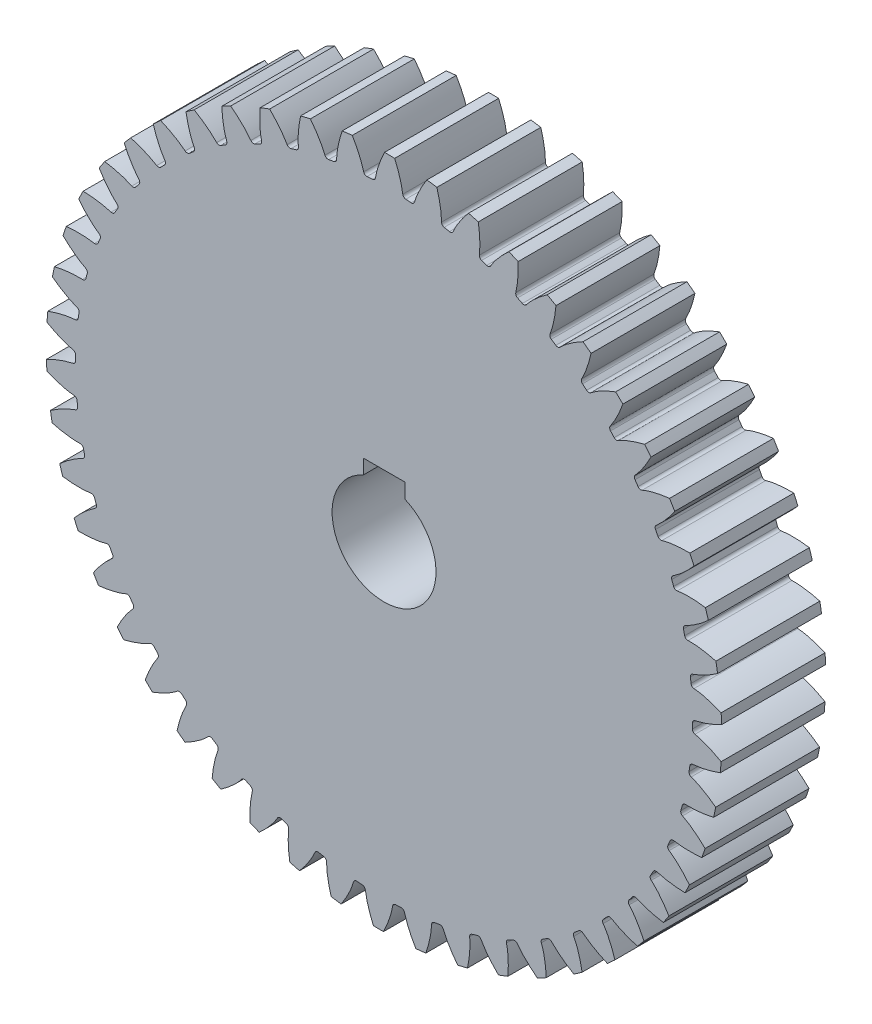
SolidWorks part; units mm, degrees
material "普通碳钢"
ref_plane "前视基准面" through (0, 0, 0) normal (0, 0, 1) x (1, 0, 0)
ref_plane "上视基准面" through (0, 0, 0) normal (0, 1, 0) x (1, 0, 0)
ref_plane "右视基准面" through (0, 0, 0) normal (1, 0, 0) x (0, 0, -1)
sketch "草图1" plane through (0, 0, 0) normal (0, 0, 1) x (1, 0, 0)
  circle A0 centre (0, 0) radius 65
  circle A1 centre (0, 0) radius 58.7308 construction
  spline S0 degree 4 poles (58.7308, 0) (58.7742, 0.0009) (58.8959, 0.0063) (59.1254, 0.0278) (59.4985, 0.0787) (59.9709, 0.1669) (60.577, 0.3073) (61.2842, 0.5066) (62.0529, 0.7609) (62.8786, 1.0748) (63.6921, 1.4211) (64.4927, 1.7963) (65.2805, 2.1977) (66.2209, 2.714) (67.331, 3.3787) (68.596, 4.2132) (69.9973, 5.2379) (71.3756, 6.3466) (72.7044, 7.5127) (73.8255, 8.5807) (74.7551, 9.5242) (75.5121, 10.3328) (76.1021, 10.9847) (76.8333, 11.8258) (77.5305, 12.661) (78.2319, 13.5487) (79.0118, 14.5714) (79.6995, 15.5266) (80.2633, 16.3317) (80.9464, 17.3657) (81.2887, 17.8975) (81.7628, 18.6537) (82.105, 19.2202) (82.4129, 19.7373) (82.5809, 20.0293) (82.6794, 20.1994) knots 0 0 0 0 0 0.005377 0.015084 0.028532 0.04661 0.064855 0.092111 0.119476 0.146842 0.174209 0.201575 0.228941 0.256307 0.307035 0.361767 0.4165 0.471232 0.525964 0.580697 0.608063 0.635429 0.662795 0.690161 0.744894 0.77226 0.799626 0.854358 0.881725 0.909091 0.931818 0.954545 0.977273 1 1 1 1 1 construction
  spline S1 degree 4 poles (58.7308, 0) (58.7742, 0.0009) (58.8959, 0.0063) (59.1254, 0.0278) (59.4985, 0.0787) (59.9709, 0.1669) (60.577, 0.3073) (61.2842, 0.5066) (62.0529, 0.7609) (62.8786, 1.0748) (63.6921, 1.4211) (64.4927, 1.7963) (65.2805, 2.1977) (66.2209, 2.714) (67.331, 3.3787) (68.596, 4.2132) (69.9973, 5.2379) (71.3756, 6.3466) (72.7044, 7.5127) (73.8255, 8.5807) (74.7551, 9.5242) (75.5121, 10.3328) (76.1021, 10.9847) (76.8333, 11.8258) (77.5305, 12.661) (78.2319, 13.5487) (79.0118, 14.5714) (79.6995, 15.5266) (80.2633, 16.3317) (80.829, 17.1879) (81.0441, 17.5188) (81.1526, 17.6879) knots 0 0 0 0 0 0.005377 0.015084 0.028532 0.04661 0.064855 0.092111 0.119476 0.146842 0.174209 0.201575 0.228941 0.256307 0.307035 0.361767 0.4165 0.471232 0.525964 0.580697 0.608063 0.635429 0.662795 0.690161 0.744894 0.77226 0.799626 0.854358 0.881725 0.909091 0.909091 0.909091 0.909091 0.909091 construction
  dimension "D1" = 130
  dimension "D2" = 117.4616
  dimension "D3" = 81.1526
extrude "凸台-拉伸1" add sketch "草图1" along normal blind 20
sketch "草图2" plane through (0, 0, 0) normal (0, 0, -1) x (-1, 0, 0)
  line L0 (0, 0) -> (-50000, 0) construction
  line L1 (24.9972, -0.3726) -> (-49969.4494, 744.8171) construction
  line L2 (0, 0) -> (-49970.4107, -825.1655) construction
  circle A0 centre (0, 0) radius 62.5 construction
  arc A1 (-59.375, 0.064) -> (-59.3405, -2.0244) centre (0, 0) ccw
  circle A2 centre (0, 0) radius 65 construction
  arc A3 (-64.9679, 2.0412) -> (-64.8651, -4.1851) centre (0, 0) ccw
  spline S0 degree 4 poles (-46.437, 1999.7444) (-50.1799, 43.412) (-53.349, 0.8372) (-56.4488, -0.3376) (-59.4985, 0.0787) (-59.9709, 0.1669) (-60.577, 0.3073) (-61.2842, 0.5066) (-62.0529, 0.7609) (-62.8786, 1.0748) (-63.6921, 1.4211) (-64.4927, 1.7963) (-65.2805, 2.1977) (-66.2209, 2.714) (-67.331, 3.3787) (-68.596, 4.2132) (-69.9973, 5.2379) (-71.3756, 6.3466) (-72.7044, 7.5127) (-73.8255, 8.5807) (-74.7551, 9.5242) (-75.5121, 10.3328) (-76.1021, 10.9847) (-76.8333, 11.8258) (-77.5305, 12.661) (-78.2319, 13.5487) (-79.0118, 14.5714) (-79.6995, 15.5266) (-81.7505, 18.4555) (-85.807, 25.1428) (-48.7954, -31.7441) (-1160.744, 1701.0672) knots -0.334457 -0.334457 -0.334457 -0.334457 -0.334457 0.005377 0.015084 0.028532 0.04661 0.064855 0.092111 0.119476 0.146842 0.174209 0.201575 0.228941 0.256307 0.307035 0.361767 0.4165 0.471232 0.525964 0.580697 0.608063 0.635429 0.662795 0.690161 0.744894 0.77226 0.799626 0.854358 0.881725 1.270064 1.270064 1.270064 1.270064 1.270064 only from (-58.7308, 0) to (-81.1526, 17.6879) construction
  spline S1 degree 4 poles (-59.375, 0.064) (-59.4427, 0.0741) (-59.6545, 0.108) (-60.01, 0.1759) (-60.577, 0.3073) (-61.2842, 0.5066) (-62.0529, 0.7609) (-62.8786, 1.0748) (-63.6921, 1.4211) (-64.3135, 1.7123) (-64.73, 1.9194) (-64.9474, 2.0306) (-64.9679, 2.0412) knots 0.020053 0.020053 0.020053 0.020053 0.020053 0.028532 0.04661 0.064855 0.092111 0.119476 0.146842 0.174209 0.201575 0.20444 0.20444 0.20444 0.20444 0.20444
  spline S2 degree 4 poles (-59.3405, -2.0244) (-59.3586, -2.0272) (-59.4891, -2.0481) (-59.7323, -2.0928) (-60.1415, -2.1825) (-60.6949, -2.3313) (-61.2969, -2.5224) (-61.9438, -2.7596) (-62.5816, -3.0221) (-63.2096, -3.3073) (-63.8278, -3.613) (-64.3173, -3.8742) (-64.6507, -4.0614) (-64.8326, -4.1663) (-64.8651, -4.1851) knots 0.025622 0.025622 0.025622 0.025622 0.025622 0.028532 0.04661 0.064855 0.092111 0.119476 0.146842 0.174209 0.201575 0.228941 0.256307 0.262277 0.262277 0.262277 0.262277 0.262277
  point P3 (-62.4931, 0.9315)
  dimension "D1" = 125
  dimension "D2" = 118.75
  dimension "D3" = 1.8
extrude "切除-拉伸1" cut sketch "草图2" against normal through all
fillet "圆角1" radius 0.625 2 edges at (59.3405, -2.0244, 10) (59.375, 0.064, 10)
pattern_circular "阵列(圆周)1" count 50 over 360 about axis through (0, 0, 20) along (0, 0, -1) of "切除-拉伸1", "圆角1"
sketch "草图3" plane through (0, 0, 0) normal (0, 0, -1) x (-1, 0, 0)
  line L0 (0, 0) -> (50000, 0) construction
  line L1 (0, 0) -> (0, -50000) construction
  line L2 (-4, 9.1652) -> (-4, 12)
  line L3 (-4, 12) -> (4, 12)
  line L4 (4, 12) -> (4, 9.1652)
  arc A0 (-4, 9.1652) -> (4, 9.1652) centre (0, 0) ccw
  dimension "D1" = 20
  dimension "D2" = 8
  dimension "D3" = 12
extrude "切除-拉伸2" cut sketch "草图3" against normal through all
equation "\"M\"= 2.5"
equation "\"Z\"= 50"
equation "\"a\"= 20"
equation "\"r\"= \"M\" * \"Z\" * cos ( \"a\" ) / 2"
equation "\"ha\"= 1"
equation "\"c\"= 0.25"
equation "\"x\"= 0"
equation "\"D1@草图1\"= \"M\" * ( \"Z\" + \"ha\" + \"ha\" + \"x\" + \"x\" ) "
equation "\"D2@草图1\"= \"r\" * 2 "
equation "\"D3@草图1\" = \"r\" * ( cos ( 180 / pi ) +  sin ( 180 / pi  ) )"
equation "\"D1@草图2\"= \"M\" * \"Z\" "
equation "\"D2@草图2\"= \"M\" * ( \"Z\" - \"ha\" - \"ha\" - \"c\" - \"c\" + \"x\" + \"x\" ) "
equation "\"D3@草图2\"= 90 / \"Z\""
equation "\"D1@圆角1\" = \"M\" / 4"
equation "\"D1@阵列(圆周)1\" = \"Z\""
